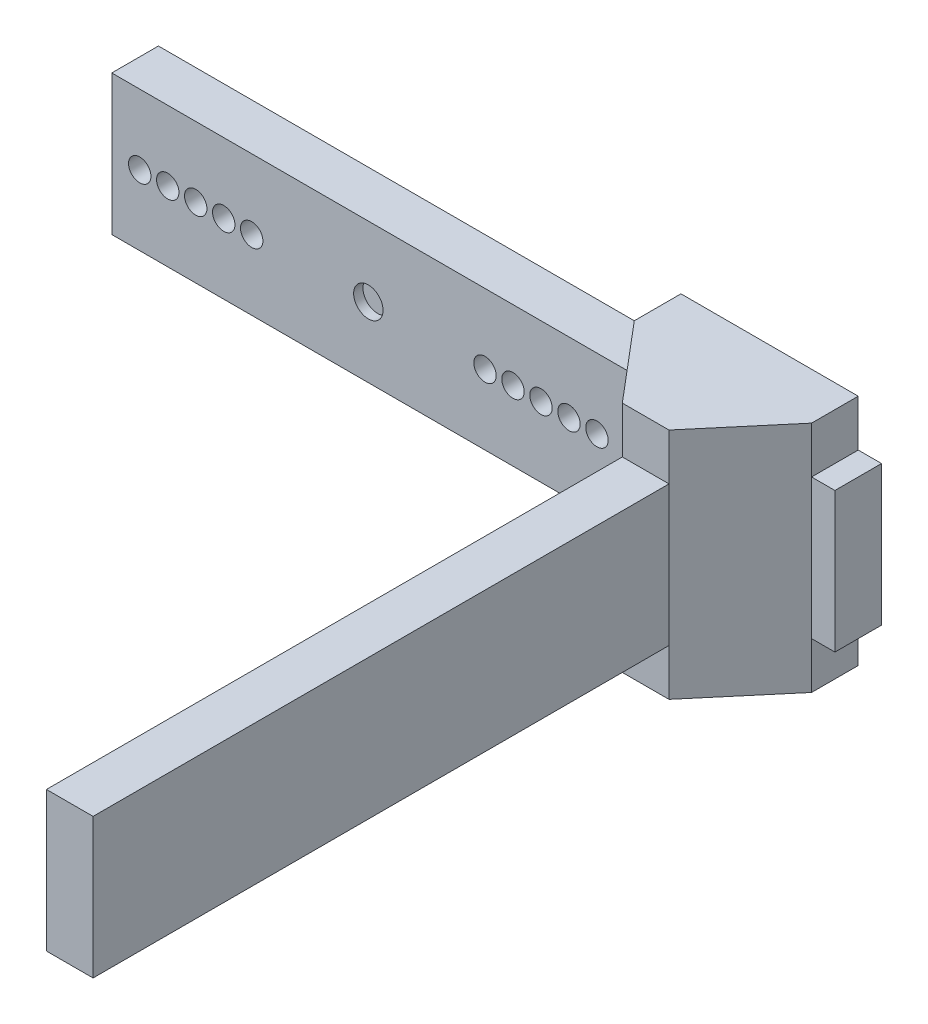
SolidWorks part; units mm, degrees
ref_plane "Front Plane" through (0, 0, 0) normal (0, 0, 1) x (1, 0, 0)
ref_plane "Top Plane" through (0, 0, 0) normal (0, 1, 0) x (1, 0, 0)
ref_plane "Right Plane" through (0, 0, 0) normal (1, 0, 0) x (0, 0, -1)
sketch "Sketch1" plane through (0, 0, 0) normal (0, 0, 1) x (1, 0, 0)
  line L0 (0, 0) -> (12.8217, 0) construction
  line L1 (-27.5, -7.5) -> (27.5, -7.5)
  line L2 (-27.5, -7.5) -> (-27.5, 7.5)
  line L3 (-27.5, 7.5) -> (27.5, 7.5)
  line L4 (27.5, -7.5) -> (27.5, 7.5)
  line L5 (-27.5, -7.5) -> (27.5, 7.5) construction
  line L6 (-27.5, 7.5) -> (27.5, -7.5) construction
  line L7 (0, 0) -> (0, -1.8994) construction
  line L9 (27.5, 7.5) -> (50, 7.5)
  line L10 (27.5, 7.5) -> (27.5, -7.5)
  line L11 (27.5, -7.5) -> (50, -7.5)
  line L12 (50, 7.5) -> (50, -7.5)
  line L13 (38.75, -7.5) -> (38.75, 7.5) construction
  line L14 (27.5, 0) -> (50, 0) construction
  circle A0 centre (24.5, 0) radius 1.2
  circle A2 centre (21.5, 0) radius 1.2
  circle A3 centre (18.5, 0) radius 1.2
  circle A4 centre (15.5, 0) radius 1.2
  circle A5 centre (12.5, 0) radius 1.2
  circle A6 centre (-24.5, 0) radius 1.2
  circle A7 centre (-21.5, 0) radius 1.2
  circle A8 centre (-18.5, 0) radius 1.2
  circle A9 centre (-15.5, 0) radius 1.2
  circle A10 centre (-12.5, 0) radius 1.2
  point P0 (0, 0)
  point P139 (38.75, 0)
  dimension "D3" = 2.4
  dimension "D4" = 3
  dimension "D5" = 50
  dimension "D1" = 55
  dimension "D2" = 15
  dimension "D6" = 5
extrude "Boss-Extrude1" add sketch "Sketch1" along normal blind 5 contours L1 L4 L3 L2 A9 A7 A0 A2 A3 A4 A5 A6 A8 A10 | L12 L9 L4 L11 region at (0, 0, 0) region at (38.75, 0, 0)
sketch "Sketch2" plane through (0, 0, 5) normal (0, 0, 1) x (1, 0, 0)
  line L0 (-11.3, 0) -> (11.3, 0) construction
  line L1 (-27.5, 7.5) -> (50, 7.5) construction
  line L2 (35.5, 7.5) -> (40.5, 7.5)
  line L3 (35.5, 7.5) -> (35.5, -7.5)
  line L4 (35.5, -7.5) -> (40.5, -7.5)
  line L5 (40.5, 7.5) -> (40.5, -7.5)
  line L6 (38, -7.5) -> (38, 7.7) construction
  line L7 (35.5, 0) -> (40.5, 0) construction
  line L8 (-27.5, -7.5) -> (50, -7.5) construction
  line L9 (-27.5, -7.5) -> (-27.5, 7.5) construction
  circle A0 centre (-12.5, 0) radius 1.2 construction
  circle A1 centre (12.5, 0) radius 1.2 construction
  circle A2 centre (0, 0) radius 1.5774
  point P146 (38, 0)
  line M5 (-27.5, -7.5) -> (50, -7.5)
  line M7 (50, 7.5) -> (-27.5, 7.5)
  dimension "D1" = 63
  dimension "D2" = 5
extrude "Cut-Extrude1" cut sketch "Sketch2" against normal blind 1 contours A2
extrude "Boss-Extrude2" add sketch "Sketch2<3>" along normal blind 70 contours L5 L3 M7 M5 region at (38, 0, 5)
sketch "Sketch2<3>" plane through (0, 0, 5) normal (0, 0, 1) x (1, 0, 0) same geometry as "Sketch2"
sketch "Sketch6" plane through (0, 7.5, 0) normal (0, 1, 0) x (1, 0, 0)
  line L0 (28.5, -5) -> (35.5, -13.2822)
  line L1 (-27.5, -5) -> (35.5, -5) construction
  line L2 (35.5, -75) -> (35.5, -5) construction
  line L3 (35.5, -13.2822) -> (35.5, -5)
  line L4 (35.5, -5) -> (28.5, -5)
  line L6 (24.2335, -5) -> (24.2335, -3.5251) construction
  dimension "D1" = 7
extrude "Boss-Extrude3" add sketch "Sketch6" against normal up to surface (15 mm away)
ref_plane "Plane2" through (38, 0, 0) normal (1, 0, 0) x (0, 0, -1)
mirror "Mirror1" about plane through (38, 0, 0) normal (1, 0, 0) of "Boss-Extrude3"
ref_plane "Plane3" through (0, 0, 0) normal (0, -1, 0) x (-1, 0, 0)
sketch "Sketch7" plane through (0, 7.5, 0) normal (0, 1, 0) x (1, 0, 0)
  line L0 (35.5, -13.2822) -> (28.5, -5)
  line L1 (28.5, -5) -> (28.5, 0)
  line L2 (-27.5, 0) -> (50, 0) construction
  line L3 (28.5, 0) -> (47.5, 0)
  line L4 (47.5, 0) -> (47.5, -5)
  line L5 (47.5, -5) -> (40.5, -13.2822)
  line L6 (40.5, -13.2822) -> (35.5, -13.2822)
extrude "Boss-Extrude4" add sketch "Sketch7" along normal blind 5
mirror "Mirror2" about plane through (0, 0, 0) normal (0, -1, 0) of "Boss-Extrude4"
